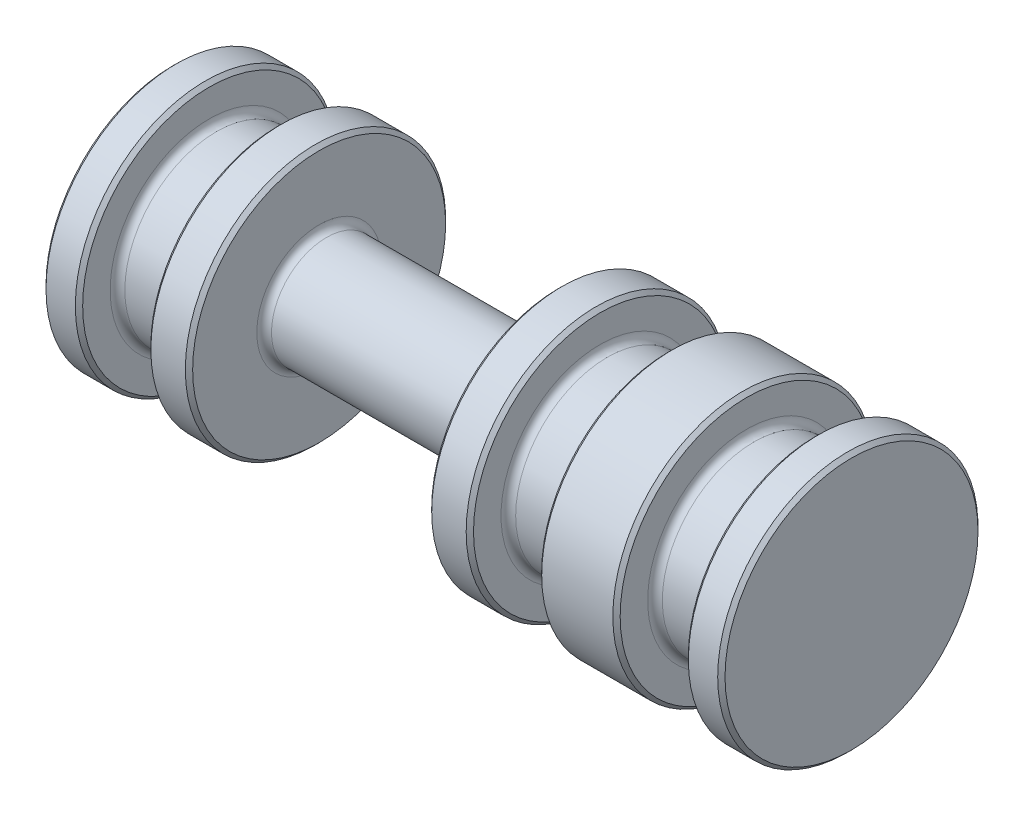
SolidWorks part; units mm, degrees
material "6063-T6"
ref_plane "Front Plane" through (0, 0, 0) normal (0, 0, 1) x (1, 0, 0)
ref_plane "Top Plane" through (0, 0, 0) normal (0, 1, 0) x (1, 0, 0)
ref_plane "Right Plane" through (0, 0, 0) normal (1, 0, 0) x (0, 0, -1)
sketch "Sketch1" plane through (0, 0, 0) normal (1, 0, 0) x (0, 0, -1)
  circle A0 centre (0, 0) radius 4.5085
  dimension "D1" = 9.017
extrude "Boss-Extrude1" add sketch "Sketch1" along normal blind 23.5204
sketch "Sketch2" plane through (0, 0, 0) normal (0, 0, 1) x (1, 0, 0)
  line L0 (-1.6174, 0) -> (23.3579, 0) construction
  line L1 (1.27, 4.5085) -> (3.6322, 4.5085)
  line L2 (3.6322, 4.5085) -> (3.6322, 3.175)
  line L3 (3.6322, 3.175) -> (1.27, 3.175)
  line L4 (1.27, 3.175) -> (1.27, 4.5085)
  line L5 (0, 4.5085) -> (0, -4.5085) construction
  line L6 (18.4404, 5.6982) -> (18.4404, -5.5364) construction
  line L7 (23.5204, -4.5085) -> (23.5204, 4.5085) construction
  line L8 (19.8882, 4.5085) -> (22.2504, 4.5085)
  line L9 (22.2504, 4.5085) -> (22.2504, 3.175)
  line L10 (22.2504, 3.175) -> (19.8882, 3.175)
  line L11 (19.8882, 3.175) -> (19.8882, 4.5085)
  line L12 (14.8082, 4.5085) -> (17.1704, 4.5085)
  line L13 (17.1704, 4.5085) -> (17.1704, 3.175)
  line L14 (17.1704, 3.175) -> (14.8082, 3.175)
  line L15 (14.8082, 3.175) -> (14.8082, 4.5085)
  line L17 (5.08, 4.5085) -> (13.3604, 4.5085)
  line L18 (5.08, 4.5085) -> (5.08, 1.905)
  line L19 (5.08, 1.905) -> (13.3604, 1.905)
  line L20 (13.3604, 4.5085) -> (13.3604, 1.905)
  dimension "D1" = 9.017
  dimension "D2" = 6.35
  dimension "D3" = 2.3622
  dimension "D4" = 1.27
  dimension "D5" = 5.08
  dimension "D6" = 1.27
  dimension "D7" = 6.35
  dimension "D8" = 5.08
  dimension "D9" = 10.16
  dimension "D10" = 3.81
  dimension "D11" = 8.2804
revolve "Cut-Revolve1" cut sketch "Sketch2" angle 360 about L0
fillet "Fillet1" radius 0.254 8 edges at (22.2504, 0, 3.175) (19.8882, 0, 3.175) (17.1704, 0, 3.175) (14.8082, 0, 3.175) (13.3604, 0, 1.905) (5.08, 0, 1.905) (3.6322, 0, 3.175) (1.27, 0, 3.175)
chamfer "Chamfer1" distance 0.127 angle 45 5 edges at (13.3604, 0, 4.5085) (0, 0, -4.5085) (22.2504, 0, 4.5085) (17.1704, 0, 4.5085) (3.6322, 0, 4.5085)
chamfer "Chamfer2" distance 0.127 angle 45 5 edges at (23.5204, 0, -4.5085) (19.8882, 0, 4.5085) (14.8082, 0, 4.5085) (5.08, 0, 4.5085) (1.27, 0, 4.5085)
sketch "Sketch3" [suppressed] plane through (22.86, 0, 0) normal (1, 0, 0) x (0, 0, -1)
  circle A0 centre (0, 0) radius 7.9117
extrude "reduce-vent" [suppressed] cut sketch "Sketch3" against normal offset from surface (5.08 mm away) 1.27 up to face at (17.1704, 0, 4.3815)
chamfer "vent-edge-break" [suppressed] distance 0.127 angle 45
